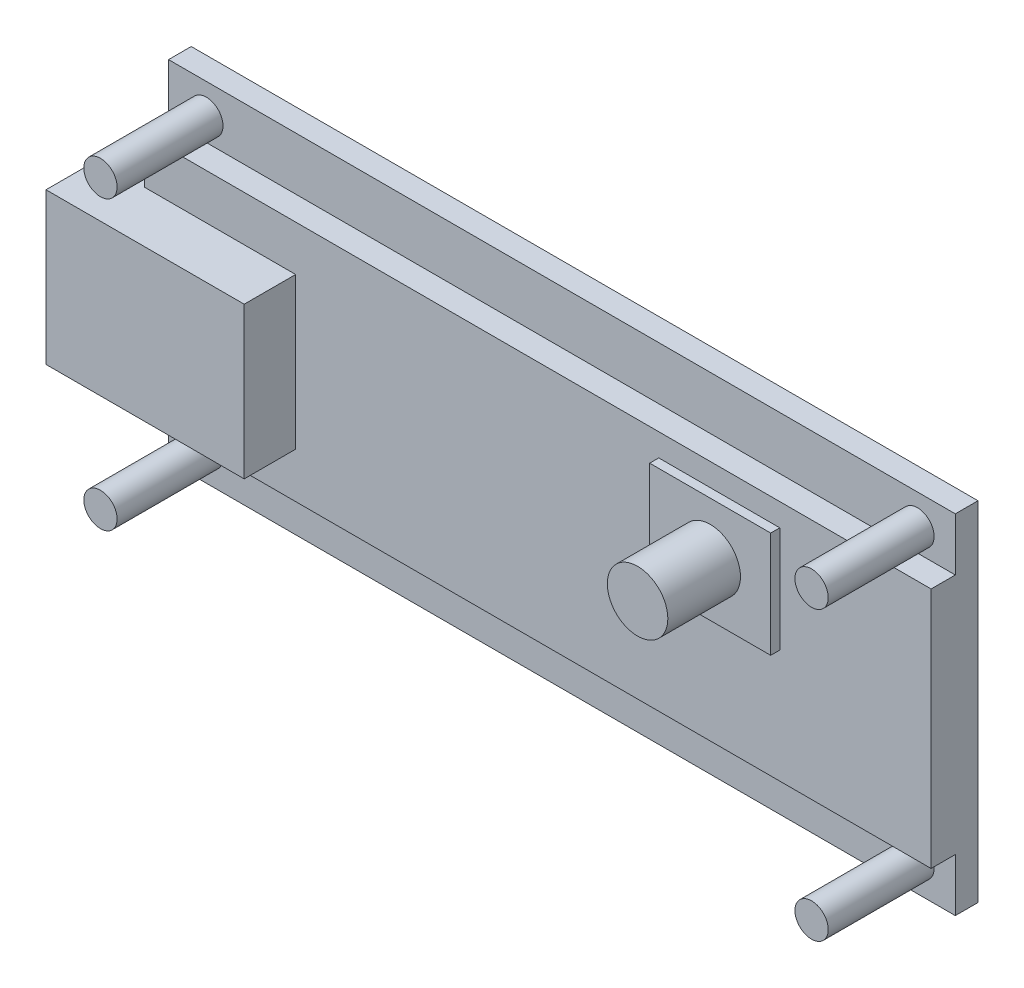
SolidWorks part; units mm, degrees
ref_plane "Front Plane" through (0, 0, 0) normal (0, 0, 1) x (1, 0, 0)
ref_plane "Top Plane" through (0, 0, 0) normal (0, 1, 0) x (1, 0, 0)
ref_plane "Right Plane" through (0, 0, 0) normal (1, 0, 0) x (0, 0, -1)
sketch "Sketch1" plane through (0, 0, 0) normal (0, 0, 1) x (1, 0, 0)
  line L0 (2.5, 21) -> (2.5, 23) construction
  line L1 (0, 0) -> (52, 0)
  line L2 (0, 0) -> (0, 23)
  line L3 (0, 23) -> (52, 23)
  line L4 (52, 0) -> (52, 23)
  line L5 (2.5, 21) -> (49.5, 21) construction
  line L6 (2.5, 21) -> (2.5, 2) construction
  line L7 (2.5, 2) -> (49.5, 2) construction
  line L8 (49.5, 21) -> (49.5, 2) construction
  line L9 (2.5, 2) -> (2.5, 0) construction
  line L10 (2.5, 2) -> (0, 2) construction
  line L11 (49.5, 2) -> (52, 2) construction
  circle A0 centre (2.5, 21) radius 1.1
  circle A1 centre (49.5, 21) radius 1.1
  circle A2 centre (2.5, 2) radius 1.1
  circle A3 centre (49.5, 2) radius 1.1
  dimension "D3" = 2.2
  dimension "D1" = 52
  dimension "D2" = 23
  dimension "D4" = 19
  dimension "D5" = 47
extrude "ext PCB" add sketch "Sketch1" against normal blind 1.5
sketch "Sketch2" plane through (0, 0, 0) normal (0, 0, 1) x (1, 0, 0)
  line L0 (0, 23) -> (0, 0) construction
  line L1 (-1.1, 16.5) -> (10, 16.5)
  line L2 (-1.1, 16.5) -> (-1.1, 6.5)
  line L3 (-1.1, 6.5) -> (10, 6.5)
  line L4 (10, 16.5) -> (10, 6.5)
  line L5 (52, 11.5) -> (0, 11.5) construction
  line L6 (52, 0) -> (52, 23) construction
  dimension "D1" = 1.1
  dimension "D2" = 10
  dimension "D3" = 10
extrude "ext USB socket" add sketch "Sketch2" along normal blind 5
sketch "Sketch3" plane through (0, 0, 0) normal (0, 0, 1) x (1, 0, 0)
  line L0 (52, 0) -> (52, 23) construction
  line L1 (52, 3.5) -> (0, 3.5)
  line L2 (52, 3.5) -> (52, 19.5)
  line L3 (52, 19.5) -> (0, 19.5)
  line L4 (0, 3.5) -> (0, 19.5)
  line L6 (0, 23) -> (0, 16.5) construction
  line L7 (0, 0) -> (52, 0) construction
  line L8 (52, 23) -> (0, 23) construction
  dimension "D1" = 3.5
  dimension "D2" = 3.5
extrude "ext Components" add sketch "Sketch3" along normal blind 1.6
sketch "Sketch4" plane through (0, 0, 0) normal (0, 0, 1) x (1, 0, 0)
  line L0 (52, 19.5) -> (52, 23) construction
  line L1 (34, 11) -> (42, 11)
  line L2 (34, 11) -> (34, 18)
  line L3 (34, 18) -> (42, 18)
  line L4 (42, 11) -> (42, 18)
  line L5 (52, 23) -> (0, 23) construction
  line L6 (38, 11) -> (38, 18) construction
  circle A0 centre (38, 14.5) radius 2
  dimension "D5" = 4
  dimension "D1" = 10
  dimension "D2" = 5
  dimension "D3" = 7
  dimension "D4" = 8
extrude "ext Reset button" add sketch "Sketch4" along normal blind 2.2 contours L4 L3 L2 L1
extrude "ext Reset Button Peg" add sketch "Sketch4<3>" along normal blind 7 contours A0
sketch "Sketch4<3>" plane through (0, 0, 0) normal (0, 0, 1) x (1, 0, 0) same geometry as "Sketch4"
sketch "Sketch5" plane through (-1.1, 0, 0) normal (-1, 0, 0) x (0, 0, 1)
  line L0 (5, 16.5) -> (5, 6.5) construction
  line L1 (0.3, 6.8) -> (4.7, 6.8)
  line L2 (0.3, 6.8) -> (0.3, 16.2)
  line L3 (0.3, 16.2) -> (4.7, 16.2)
  line L4 (4.7, 6.8) -> (4.7, 16.2)
  line L5 (0, 16.5) -> (0, 6.5) construction
  line L6 (5, 6.5) -> (0, 6.5) construction
  line L7 (5, 16.5) -> (0, 16.5) construction
  dimension "D1" = 0.3
  dimension "D2" = 0.3
  dimension "D3" = 0.3
  dimension "D4" = 0.3
extrude "ext USB Plug" add sketch "Sketch5" along normal blind 2
sketch "Sketch6" plane through (0, 0, 0) normal (-1, 0, 0) x (0, 0, 1)
  line L0 (5, 6.5) -> (1.6, 6.5)
  line L1 (1.6, 6.5) -> (0, 6.5)
  line L3 (5, 6.5) -> (-1.5, 6.5)
  line L4 (5, 6.5) -> (5, 16.5)
  line L5 (5, 6.5) -> (5, 16.5)
  line L6 (0, 16.5) -> (1.6, 16.5)
  line L7 (1.6, 16.5) -> (5, 16.5)
  line L8 (-1.5, 16.5) -> (5, 16.5)
  line L22 (0, 19.5) -> (0, 23)
  line L23 (0, 23) -> (-1.5, 23)
  line L24 (-1.5, 23) -> (-1.5, 0)
  line L25 (-1.5, 0) -> (0, 0)
  line L26 (0, 0) -> (0, 3.5)
  line L27 (0, 3.5) -> (1.6, 3.5)
  line L28 (1.6, 3.5) -> (1.6, 6.5)
  line L29 (1.6, 6.5) -> (0, 6.5)
  line L30 (0, 6.5) -> (0, 16.5)
  line L31 (0, 16.5) -> (1.6, 16.5)
  line L32 (1.6, 16.5) -> (1.6, 19.5)
  line L33 (1.6, 19.5) -> (0, 19.5)
  line L36 (-1.5, 16.5) -> (-1.5, 6.5)
  line M15 (-1.5, 23) -> (-1.5, 0)
  line M20 (1.6, 6.5) -> (0, 6.5)
  line M21 (0, 6.5) -> (0, 16.5)
  line M22 (0, 16.5) -> (1.6, 16.5)
  dimension "D1" = 0
extrude "ext USB slot" add sketch "Sketch6" along normal up to vertex (3.1 mm away) contours L8 L3 L5 M22 M21 M20 | L8 L3 M15 M21 region at (0, 11.5, 2.5) region at (0, 11.5, -0.75) up to point (-3.1, 16.2, 4.7)
sketch "Sketch7" plane through (0, 0, 0) normal (0, 0, 1) x (1, 0, 0)
  circle A0 centre (49.5, 2) radius 1.1 construction
  circle A1 centre (2.5, 2) radius 1.1 construction
  circle A2 centre (2.5, 21) radius 1.1 construction
  circle A3 centre (49.5, 21) radius 1.1 construction
  circle A4 centre (49.5, 2) radius 1.1
  circle A5 centre (2.5, 2) radius 1.1
  circle A6 centre (2.5, 21) radius 1.1
  circle A7 centre (49.5, 21) radius 1.1
extrude "ext Mounts " add sketch "Sketch7" along normal through all and the other way up to surface (1.5 mm away) other way up to face at (50.6, 2, -1.5)
equation "\"D2@Sketch3\"=\"D1@Sketch3\""
